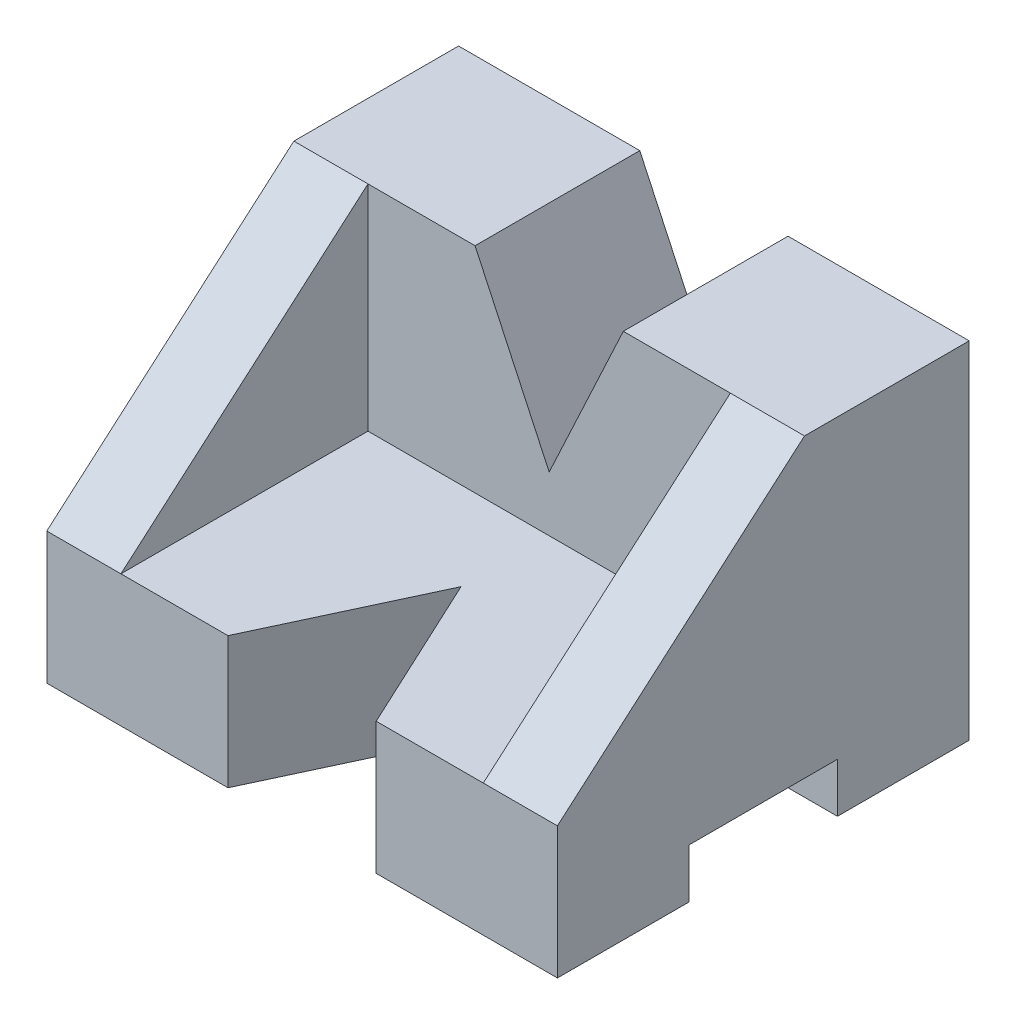
SolidWorks part; units mm, degrees
material "Cast Alloy Steel"
ref_plane "Front Plane" through (0, 0, 0) normal (0, 0, 1) x (1, 0, 0)
ref_plane "Top Plane" through (0, 0, 0) normal (0, 1, 0) x (1, 0, 0)
ref_plane "Right Plane" through (0, 0, 0) normal (1, 0, 0) x (0, 0, -1)
sketch "Sketch2" plane through (0, 0, 0) normal (1, 0, 0) x (0, 0, -1)
  line L0 (5, 21) -> (25, 21)
  line L1 (25, 21) -> (25, -21)
  line L2 (25, -21) -> (9, -21)
  line L3 (9, -21) -> (9, -15)
  line L4 (9, -15) -> (-9, -15)
  line L5 (-9, -15) -> (-9, -21)
  line L6 (-9, -21) -> (-25, -21)
  line L7 (-25, -21) -> (-25, -5)
  line L8 (-25, -5) -> (5, -5)
  line L9 (5, -5) -> (5, 21)
  dimension "D1" = 25
  dimension "D2" = 21
  dimension "D3" = 42
  dimension "D4" = 20
  dimension "D5" = 16
  dimension "D6" = 16
  dimension "D7" = 16
  dimension "D8" = 50
  dimension "D9" = 6
  dimension "D10" = 6
extrude "Boss-Extrude2" add sketch "Sketch2" along normal mid plane 62
sketch "Sketch3" plane through (0, 0, 0) normal (1, 0, 0) x (0, 0, -1)
  line L0 (5, 21) -> (-25, -5)
  line L1 (-25, -5) -> (5, -5)
  line L2 (5, -5) -> (5, 21)
extrude "Boss-Extrude3" add sketch "Sketch3" along normal blind 9 from offset 22
extrude "Boss-Extrude4" add sketch "Sketch3<4>" against normal blind 9 from offset 22 offset against normal yes
sketch "Sketch3<4>" plane through (0, 0, 0) normal (1, 0, 0) x (0, 0, -1) same geometry as "Sketch3"
sketch "Sketch4" plane through (0, 0, 0) normal (0, 1, 0) x (1, 0, 0)
  line L0 (-9, -25) -> (0, -5.6994)
  line L1 (22, -25) -> (-22, -25) construction
  line L2 (0, -5.6994) -> (9, -25)
  line L3 (-31, 5) -> (-31, -25) construction
  line L4 (31, 5) -> (31, -25) construction
  line L5 (-9, -25) -> (9, -25)
  dimension "D1" = 22
  dimension "D2" = 22
  dimension "D3" = 65
  dimension "D4" = 65
extrude "Cut-Extrude3" cut sketch "Sketch4" against normal through all
sketch "Sketch6" plane through (0, 0, 0) normal (0, 0, 1) x (1, 0, 0)
  line L0 (-9, 21) -> (0, 1.6994)
  line L1 (22, 21) -> (-22, 21) construction
  line L2 (0, 1.6994) -> (9, 21)
  line L3 (9, 21) -> (-9, 21)
  line L4 (31, 21) -> (31, -5) construction
  dimension "D1" = 22
  dimension "D2" = 22
  dimension "D3" = 65
  dimension "D4" = 65
extrude "Cut-Extrude4" cut sketch "Sketch6" against normal through all
equation "\"f\"=9"
